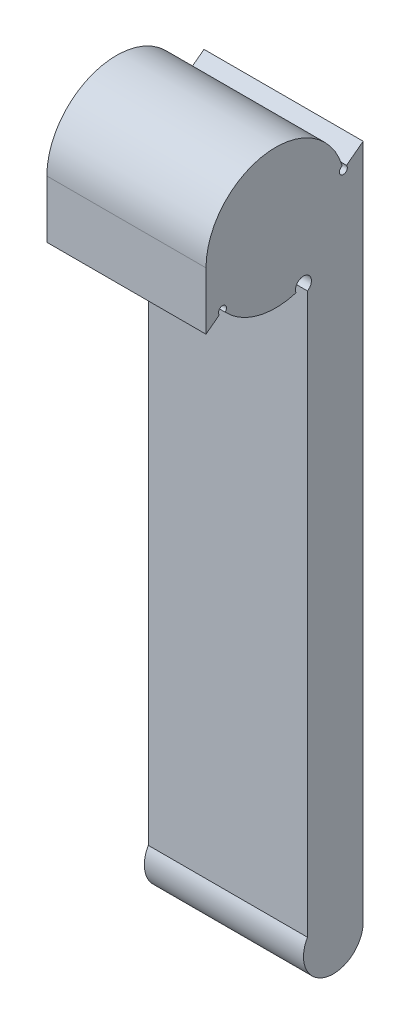
SolidWorks part; units mm, degrees
ref_plane "Front Plane" through (0, 0, 0) normal (1, 0, 0) x (0, 1, 0)
ref_plane "Top Plane" through (0, 0, 0) normal (0, 0, 1) x (0, 1, 0)
ref_plane "Right Plane" through (0, 0, 0) normal (0, 1, 0) x (-1, 0, 0)
sketch "Sketch1" plane through (0, 0, 0) normal (1, 0, 0) x (0, 1, 0)
  line L0 (24.6661, -15.2608) -> (21.7782, -15.2608)
  line L1 (21.7782, -15.2608) -> (22.4034, -16.0905)
  line L2 (22.4034, -16.0905) -> (24.6661, -15.2608)
  line L3 (24.6661, -18.7608) -> (21.1661, -18.7608) construction
  line L4 (25.4785, -22.1652) -> (26.2287, -23.1608)
  line L5 (26.2287, -23.1608) -> (-7.7713, -23.1608)
  line L7 (-7.7713, -20.1608) -> (21.4583, -20.1608)
  line L8 (25.4785, -22.1652) -> (21.4583, -20.1608)
  circle A0 centre (24.6661, -18.7608) radius 3.5
  circle A1 centre (24.6661, -18.7608) radius 0.2
  circle A2 centre (24.6661, -18.7608) radius 1.4
  arc A3 (-7.7713, -20.1608) -> (-7.7713, -23.1608) centre (-7.7713, -21.6608) ccw
  dimension "D1" = 7
  dimension "D2" = 0.4
  dimension "D3" = 2.8
  dimension "D4" = 53
  dimension "D5" = 3
  dimension "D6" = 34
extrude "Boss-Extrude1" add sketch "Sketch1" along normal blind 8 contours L7 A3 L5 L4 A0 | L8 A0 | A2 A0 L8 L2 | A0 L0 L1 | L2 A0 | A1 A2 | A1 region at (0, 22.7235, -15.5139) region at (0, 27.0714, -16.3554) region at (0, 23.5052, -15.5951) region at (0, 7.2829, -21.705) region at (0, 23.3212, -21.4581) region at (0, 24.6661, -18.7608) region at (0, 23.3057, -18.7608)
sketch "Sketch2" plane through (0, 0, 0) normal (-1, 0, 0) x (0, -1, 0)
  line L0 (-21.7782, -15.2608) -> (-22.4034, -16.0905) construction
  line L1 (-22.2546, -16.2241) -> (-22.2831, -15.9307)
  line L2 (-25.4785, -22.1652) -> (-26.2287, -23.1608) construction
  line L3 (-25.5989, -22.3249) -> (-25.6716, -22.1132)
  line L6 (7.7713, -20.1608) -> (-21.4583, -20.1608) construction
  line L7 (-21.1119, -20.3608) -> (7.0229, -20.3608)
  line L8 (-21.1119, -20.3608) -> (-21.4583, -20.1608)
  line L9 (-21.3195, -19.7856) -> (-21.3195, -20.1608)
  line L10 (-21.3195, -20.1608) -> (7.7713, -20.1608)
  arc A0 (-22.2831, -15.9307) -> (-22.2546, -16.2241) centre (-22.4034, -16.0905) ccw
  arc A1 (-21.4583, -20.1608) -> (-22.4034, -16.0905) centre (-24.6661, -18.7608) ccw construction
  arc A2 (-25.5989, -22.3249) -> (-25.6716, -22.1132) centre (-25.4785, -22.1652) ccw
  arc A3 (-24.6661, -15.2608) -> (-25.4785, -22.1652) centre (-24.6661, -18.7608) ccw construction
  arc A4 (-21.1119, -20.3608) -> (-21.3195, -19.7856) centre (-21.4583, -20.1608) cw
  arc A5 (7.7713, -20.1608) -> (7.0229, -20.3608) centre (7.7713, -21.6608) ccw
  arc A6 (7.7713, -23.1608) -> (7.7713, -20.1608) centre (7.7713, -21.6608) ccw construction
  line M11 (7.7713, -20.1608) -> (-21.4583, -20.1608)
  arc M12 (-21.4583, -20.1608) -> (-22.4034, -16.0905) centre (-24.6661, -18.7608) ccw
  line M13 (-22.4034, -16.0905) -> (-21.7782, -15.2608)
  arc M15 (-24.6661, -15.2608) -> (-25.4785, -22.1652) centre (-24.6661, -18.7608) ccw
  line M16 (-25.4785, -22.1652) -> (-26.2287, -23.1608)
  dimension "D1" = 0.2
  dimension "D2" = 0.2
  dimension "D3" = 0.4
  dimension "D4" = 0.2
extrude "Cut-Extrude1" cut sketch "Sketch2" against normal through all contours A0 M13 M12 | A4 L8 M12 | A2 M16 M15 | A5 L8 L7 M11 | L9 M12 M11 | L3 M16 M15 | L1 M12 M13 region at (0, 22.3136, -16.081) region at (0, 21.3644, -20.0396) region at (0, 21.542, -20.1903) region at (0, 22.4455, -16.0947) region at (0, 7.0095, -20.2602) region at (0, 25.451, -22.1556) region at (0, 25.5831, -22.2017)
equation "\"D1@Sketch1\"=\"stand_pivot_diameter@clock_monsieur.Assembly\""
equation "\"D2@Sketch1\"=\"stand_pivot_inset@clock_monsieur.Assembly\"*2"
equation "\"D3@Sketch1\"=\"stand_pivot_inset@clock_monsieur.Assembly\"*2+\"back_thickness@clock_monsieur.Assembly\"*2"
equation "\"D6@Sketch1\"=\"stand_length@clock_monsieur.Assembly\""
equation "\"D1@Boss-Extrude1\"=\"stand_width@clock_monsieur.Assembly\""
equation "\"D4@Sketch1\"=\"stand_max_angle@clock_monsieur.Assembly\""
equation "\"D2@Sketch2\"=\"D1@Sketch2\""
equation "\"D3@Sketch2\"=\"D1@Sketch2\"*2"
equation "\"D4@Sketch2\"=\"D1@Sketch2\""
